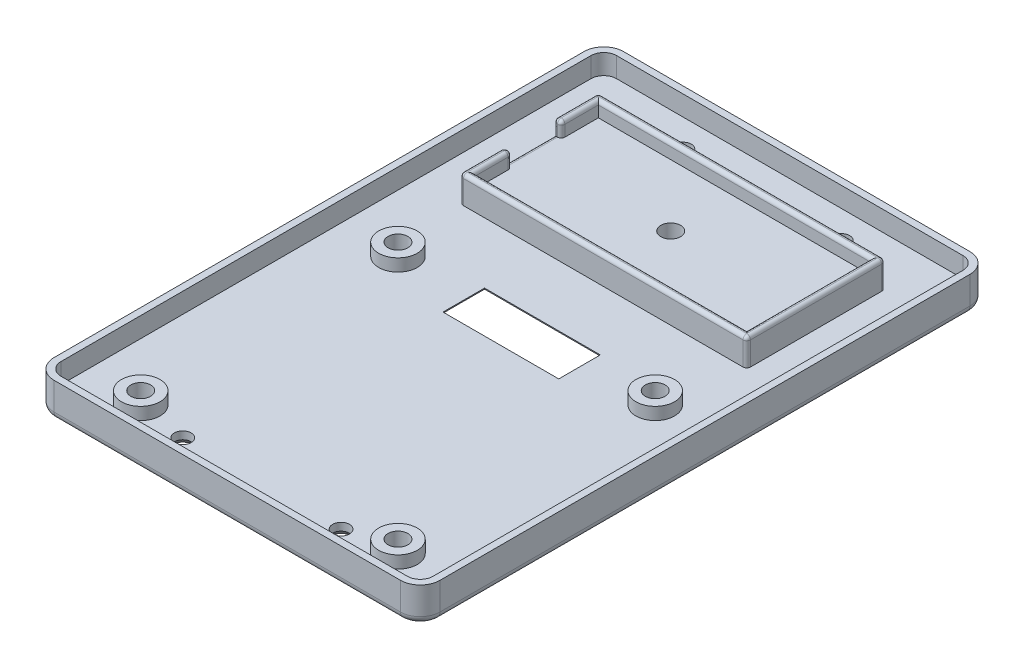
SolidWorks part; units mm, degrees
ref_plane "Plan de face" through (0, 0, 0) normal (0, 0, 1) x (1, 0, 0)
ref_plane "Plan de dessus" through (0, 0, 0) normal (0, 1, 0) x (1, 0, 0)
ref_plane "Plan de droite" through (0, 0, 0) normal (1, 0, 0) x (0, 0, -1)
sketch "Esquisse1" plane through (0, 0, 0) normal (0, 1, 0) x (1, 0, 0)
  line L1 (-39, 0) -> (39, 0)
  line L2 (-39, 0) -> (-39, 115.1)
  line L3 (-39, 115.1) -> (39, 115.1)
  line L4 (39, 0) -> (39, 115.1)
  point P4 (0, 0)
  dimension "D1" = 78
  dimension "D2" = 115.1
extrude "Bottom_WithPCB" add sketch "Esquisse1" along normal blind 7.05
fillet "Box_Corners" radius 4 4 edges at (39, 3.525, -115.1) (-39, 3.525, -115.1) (-39, 3.525, 0) (39, 3.525, 0)
fillet "Congé2" radius 1.5 8 edges at (-37.8284, 0, -113.9284) (-39, 0, -57.55) (-37.8284, 0, -1.1716) (0, 0, 0) (37.8284, 0, -1.1716) (39, 0, -57.55) (37.8284, 0, -113.9284) (0, 0, -115.1)
shell "Inside_Hole" thickness 3 removed face at (0, 7.05, -57.55)
sketch "Esquisse5" plane through (0, 7.05, 0) normal (0, 1, 0) x (1, 0, 0)
  line L8 (37.6, 4) -> (37.6, 111.1)
  line L9 (35, 113.7) -> (-35, 113.7)
  line L10 (-37.6, 111.1) -> (-37.6, 4)
  line L11 (-35, 1.4) -> (35, 1.4)
  line L12 (37.6, 4) -> (37.6, 111.1)
  line L13 (35, 113.7) -> (-35, 113.7)
  line L14 (-37.6, 111.1) -> (-37.6, 4)
  line L15 (-35, 1.4) -> (35, 1.4)
  arc A8 (37.6, 111.1) -> (35, 113.7) centre (35, 111.1) ccw
  arc A9 (37.6, 111.1) -> (35, 113.7) centre (35, 111.1) ccw
  arc A10 (-35, 113.7) -> (-37.6, 111.1) centre (-35, 111.1) ccw
  arc A11 (-35, 113.7) -> (-37.6, 111.1) centre (-35, 111.1) ccw
  arc A12 (-37.6, 4) -> (-35, 1.4) centre (-35, 4) ccw
  arc A13 (-37.6, 4) -> (-35, 1.4) centre (-35, 4) ccw
  arc A14 (35, 1.4) -> (37.6, 4) centre (35, 4) ccw
  arc A15 (35, 1.4) -> (37.6, 4) centre (35, 4) ccw
  dimension "D1" = 1.4
extrude "Border_Notch" cut sketch "Esquisse5" against normal blind 4.05
sketch "Col_Position" plane through (0, 3, 0) normal (0, 1, 0) x (1, 0, 0)
  circle A0 centre (-26, 8.5) radius 3.9
  dimension "D1" = 7.8
  dimension "D2" = 26
  dimension "D3" = 8.5
extrude "Col_PCB" add sketch "Col_Position" along normal blind 2.5
sketch "Esquisse4" plane through (0, 5.5, 0) normal (0, 1, 0) x (1, 0, 0)
  circle A0 centre (-26, 8.5) radius 2
  dimension "D1" = 4
extrude "Insert_Hole_In_Col" cut sketch "Esquisse4" against normal blind 4
mirror "Symétrie1" about plane through (0, 0, 0) normal (1, 0, 0) of "Col_PCB", "Insert_Hole_In_Col"
pattern_linear "Répétition linéaire1" count 2 spacing 52 along (0, 0, -1) of "Symétrie1"
hole_wizard "Fraisage pour vis à tête fraisée M31" positions "Esquisse6" profile "Esquisse7" countersink size "M3" standard "Ansi Metric" end condition through all
sketch "Esquisse6" plane through (0, 0, 0) normal (0, -1, 0) x (-1, 0, 0)
  line L1 (-16, 7) -> (16, 7) construction
  line L2 (16, 7) -> (16, 108.1) construction
  line L3 (16, 108.1) -> (-16, 108.1) construction
  line L4 (-16, 108.1) -> (-16, 7) construction
  line L6 (0, 0) -> (0, 7) construction
  point P0 (-16, 7)
  point P2 (16, 7)
  point P4 (16, 108.1)
  point P6 (-16, 108.1)
  dimension "D2" = 32
  dimension "D3" = 108.1
sketch "Esquisse7" plane through (16, 0, -7) normal (1, 0, 0) x (0, 0, -1)
  line L0 (0, 0) -> (0, 7.05)
  line L1 (0, 7.05) -> (1.7, 7.05)
  line L2 (1.7, 7.05) -> (1.7, 1.45)
  line L3 (1.7, 1.45) -> (3.15, 0)
  line L5 (3.15, 0) -> (0, 0)
  line L6 (-1.7, 1.45) -> (-3.15, 0) construction
  line L11 (0, -6.35) -> (0, 107.95) construction
  dimension "Diamètre du perçage jusqu'au prochain" = 3.4
  dimension "Profondeur du perçage jusqu'au prochain" = 7.05
  dimension "Diamètre du fraisage entrant" = 6.3
  dimension "Angle du fraisage entrant" = 90
sketch "Esquisse8" plane through (0, 3, 0) normal (0, 1, 0) x (1, 0, 0)
  line L0 (-22.1, 60.5) -> (22.1, 60.5) construction
  line L1 (-11.7, 59.5) -> (11.7, 59.5) construction
  line L2 (-11.7, 55.3) -> (11.7, 55.3)
  line L3 (-11.7, 55.3) -> (-11.7, 63.7)
  line L4 (-11.7, 63.7) -> (11.7, 63.7)
  line L5 (11.7, 55.3) -> (11.7, 63.7)
  line L6 (0, 60.5) -> (0, 59.5) construction
  circle A0 centre (-26, 60.5) radius 3.9 construction
  circle A1 centre (-26, 60.5) radius 3.9 construction
  circle A2 centre (26, 60.5) radius 3.9 construction
  dimension "D1" = 23.4
  dimension "D2" = 8.4
extrude "Solar_Opening" cut sketch "Esquisse8" against normal through all
chamfer "Chanfrein1" distance 2.8 angle 45 4 edges at (-11.7, 0, -59.5) (0, 0, -55.3) (0, 0, -63.7) (11.7, 0, -59.5)
sketch "Esquisse9" plane through (0, 3, 0) normal (0, 1, 0) x (1, 0, 0)
  line L0 (-29, 76) -> (29, 76) construction
  line L1 (29, 76) -> (29, 104) construction
  line L2 (29, 104) -> (-29, 104) construction
  line L3 (-29, 104) -> (-29, 76) construction
  line L4 (-29, 90) -> (29, 90) construction
  line L5 (0, 76) -> (0, 0) construction
  line L6 (-29, 104) -> (-29, 90)
  line L14 (-29, 90) -> (-29, 76)
  line L15 (-29, 76) -> (29, 76)
  line L16 (29, 76) -> (29, 104)
  line L17 (29, 104) -> (-29, 104)
  point P9 (0, 0)
  point P11 (0, 0)
  point P22 (-27, 83.9527)
  dimension "D1" = 58
  dimension "D2" = 28
  dimension "D3" = 76
extrude "Boss.-Extru.1" add sketch "Esquisse9" along normal blind 2.5
sketch "Esquisse10" plane through (0, 5.5, 8) normal (0, 1, 0) x (1, 0, 0)
  line L0 (-29, 84) -> (29, 84) construction
  line L1 (29, 84) -> (29, 112) construction
  line L2 (29, 112) -> (-29, 112) construction
  line L3 (-29, 112) -> (-29, 84) construction
  line L4 (-29, 98) -> (29, 98) construction
  line L5 (0, 84) -> (0, 8) construction
  line L6 (-29, 112) -> (-29, 103)
  line L7 (-29, 103) -> (-27.5, 103)
  line L8 (-27.5, 103) -> (-27.5, 110.5)
  line L9 (-27.5, 110.5) -> (27.5, 110.5)
  line L10 (27.5, 110.5) -> (27.5, 85.5)
  line L11 (27.5, 85.5) -> (-27.5, 85.5)
  line L12 (-27.5, 85.5) -> (-27.5, 93)
  line L13 (-27.5, 93) -> (-29, 93)
  line L14 (-29, 93) -> (-29, 84)
  line L15 (-29, 84) -> (29, 84)
  line L16 (29, 84) -> (29, 112)
  line L17 (29, 112) -> (-29, 112)
  line L18 (-27.5, 103) -> (-27.5, 93) construction
  line L19 (27.5, 85.5) -> (27.5, 84) construction
  line L20 (27.5, 110.5) -> (27.5, 112) construction
  line L21 (-27.5, 110.5) -> (-29, 110.5) construction
  line L22 (-27.5, 85.5) -> (-29, 85.5) construction
  line L23 (27.5, 85.5) -> (29, 85.5) construction
  point P18 (-27.5, 98)
  point P22 (-27, 83.9527)
  point P24 (0, 5.2363)
  point P26 (0, 0)
  dimension "D1" = 58
  dimension "D2" = 28
  dimension "D3" = 76
  dimension "D4" = 1.5
  dimension "D5" = 10
extrude "Boss.-Extru.2" add sketch "Esquisse10" along normal blind 3
fillet "Congé3" radius 0.75 21 edges at (-29, 5.75, -104) (29, 5.75, -104) (29, 5.75, -76) (-29, 5.75, -76) (-29, 7, -85) (-27.5, 7, -85) (-27.5, 7, -95) (-29, 7, -95) (-29, 8.5, -80.5) (-27.5, 8.5, -81.25) (0, 8.5, -77.5) (27.5, 8.5, -90) (0, 8.5, -102.5) (-27.5, 8.5, -98.75) (-29, 8.5, -99.5) (0, 8.5, -104) (29, 8.5, -90) (0, 8.5, -76) (-29, 5.5, -90) (-28.25, 8.5, -85) (-28.25, 8.5, -95)
sketch "Esquisse11" plane through (0, 5.5, 0) normal (0, 1, 0) x (1, 0, 0)
  line L0 (-28.25, 90) -> (27.5, 90) construction
  line L1 (-28.25, 95) -> (-28.25, 85) construction
  line L2 (27.5, 102.5) -> (27.5, 77.5) construction
  circle A0 centre (-0.375, 90) radius 2
  dimension "D1" = 4
extrude "Enlèv. mat.-Extru.1" cut sketch "Esquisse11" against normal blind 4
sketch "Esquisse12" plane through (0, 0, 0) normal (0, -1, 0) x (1, 0, 0)
  line L1 (37.5, -111.1) -> (37.5, -4) construction
  line L4 (37.5, -26.7) -> (37.5, -81.25) construction
  line L6 (-37.5, -26.7) -> (37.5, -26.7) construction
  line L7 (-37.5, -4) -> (-37.5, -111.1) construction
  line L10 (-37.5, -81.25) -> (37.5, -81.25) construction
  text T0 "ETML-ES\r\nSLO2-23" font "Consolas" height 8
  text T1 "\r\nMiguel Santos" font "Century Gothic" height 6
  text T2 "2228 Alarme fenêtre V1" font "Century Gothic" height 4
  point P0 (34, -83.5)
  dimension "D1" = 26.7
  dimension "D2" = 54.55
extrude "Enlèv. mat.-Extru.2" cut sketch "Esquisse12" against normal blind 0.4
equation "\"PCB_Length_Y\"= 60mm"
equation "\"PCB_Width_X\"= 60mm"
equation "\"PCB_Thickness_Z\"= 1.55mm"
equation "\"PCB_Pos_Y\"= 5mm"
equation "\"PCB_Zone_Y\"= \"PCB_Length_Y\" + \"Box_Wall_Thickness\" 'Zone occupée par le PCB centrée au milieu de la zone"
equation "\"PCB_Zone_X\"= \"PCB_Width_X\" + 12mm"
equation "\"Battery_Zone_Y\"= \"Battery_Length_Y\" + \"Box_Wall_Thickness\" + \"Fixation_holes_offset\" + \"Col_Diameter\"/2 + \"Battery_Offset\" + \"Global_Gap\"*2"
equation "\"Battery_Length_Y\"= 25mm"
equation "\"Battery_Width_X\"= 55mm"
equation "\"Box_Wall_Thickness\"= 3mm"
equation "\"Box_Border_Height\"= \"Col_Height\" + \"PCB_Thickness_Z\""
equation "\"Box_Corner_Radius\"= 4mm"
equation "\"PCB_Holes_X\"= 52mm"
equation "\"PCB_Holes_Y\"= 52mm"
equation "\"Col_Height\"= 2.5mm"
equation "\"Box_Bottom_Thick\"= 3mm"
equation "\"Box_Top_Thick\"= 3mm"
equation "\"PCB_Components_Height\"= 22mm"
equation "\"Global_Gap\"= 0.1mm"
equation "\"Col_Diameter\"= 7.8mm"
equation "\"D1@Esquisse1\"=\"PCB_Zone_X\"+2 * \"Box_Wall_Thickness\""
equation "\"D2@Esquisse1\"=2 * \"Box_Wall_Thickness\" + \"PCB_Zone_Y\" + \"Battery_Zone_Y\""
equation "\"D1@Bottom_WithPCB\" = \"Box_Bottom_Thick\" + \"Box_Border_Height\""
equation "\"D1@Box_Corners\"=\"Box_Corner_Radius\""
equation "\"D1@Inside_Hole\"=\"Box_Wall_Thickness\""
equation "\"D2@Inside_Hole\"= \"Box_Bottom_Thick\""
equation "\"D1@Col_Position\" = \"Col_Diameter\""
equation "\"D2@Col_Position\"= \"PCB_Holes_X\" / 2"
equation "\"D3@Col_Position\" =  ( \"PCB_Zone_Y\" - \"PCB_Holes_Y\" )  / 2 + \"Box_Wall_Thickness\""
equation "\"D1@Col_PCB\" = \"Col_Height\""
equation "\"D3@Répétition linéaire1\"=\"PCB_Holes_Y\""
equation "\"Inserts_Diameter\"= 4mm"
equation "\"Inserts_Height\"= 4mm"
equation "\"D1@Esquisse4\"=\"Inserts_Diameter\""
equation "\"D1@Insert_Hole_In_Col\" = \"Inserts_Height\""
equation "\"D1@Esquisse5\"=\"Box_Wall_Thickness\"/2 - \"Global_Gap\""
equation "\"D1@Border_Notch\" = \"Box_Border_Height\""
equation "\"Fixation_holes_X\"= 32mm"
equation "\"Fixation_holes_offset\"= 4mm'Distance from inside border of hole center"
equation "\"D2@Esquisse6\"=\"Fixation_holes_X\""
equation "\"Solar_Width_X\"= 23.4mm"
equation "\"Solar_Length_Y\"= 8.4mm"
equation "\"D1@Esquisse8\"=\"Solar_Width_X\""
equation "\"D2@Esquisse8\"=\"Solar_Length_Y\""
equation "\"D1@Chanfrein1\"=\"Box_Bottom_Thick\" - \"Global_Gap\"*2"
equation "\"D1@Congé2\"=\"Box_Bottom_Thick\"/2"
equation "\"D1@Esquisse6\"=\"Box_Wall_Thickness\"+\"Fixation_holes_offset\""
equation "\"D1@Esquisse9\"=\"Battery_Width_X\" + \"Box_Wall_Thickness\""
equation "\"D2@Esquisse9\"=\"Battery_Length_Y\" + \"Box_Wall_Thickness\""
equation "\"D1@Boss.-Extru.1\"=\"Col_Height\""
equation "\"D1@Congé3\"=\"Box_Wall_Thickness\"/4"
equation "\"D3@Esquisse6\"=\"Box_Wall_Thickness\" + \"PCB_Zone_Y\" + \"Battery_Zone_Y\" - \"Fixation_holes_offset\""
equation "\"D3@Esquisse9\"=\"Box_Wall_Thickness\"+\"PCB_Zone_Y\" + \"Battery_Offset\""
equation "\"Battery_Offset\"= 10mm"
equation "\"D1@Boss.-Extru.2\"=\"Box_Wall_Thickness\""
equation "\"D1@Esquisse11\"=\"Inserts_Diameter\""
equation "\"D1@Enlèv. mat.-Extru.1\"=\"Inserts_Height\""
equation "\"D1@Esquisse12\"=\"Box_Wall_Thickness\"+\"PCB_Zone_Y\"/2 - \"Col_Diameter\""
equation "\"D2@Esquisse12\"=(\"PCB_Zone_Y\"+\"Battery_Zone_Y\")/2"
equation "\"D3@Esquisse10\"=\"Box_Wall_Thickness\"+\"PCB_Zone_Y\" + \"Battery_Offset\""
equation "\"D1@Esquisse10\"=\"Battery_Width_X\" + \"Box_Wall_Thickness\""
equation "\"D2@Esquisse10\"=\"Battery_Length_Y\" + \"Box_Wall_Thickness\""
equation "\"D4@Esquisse10\"=\"Box_Wall_Thickness\"/2"
